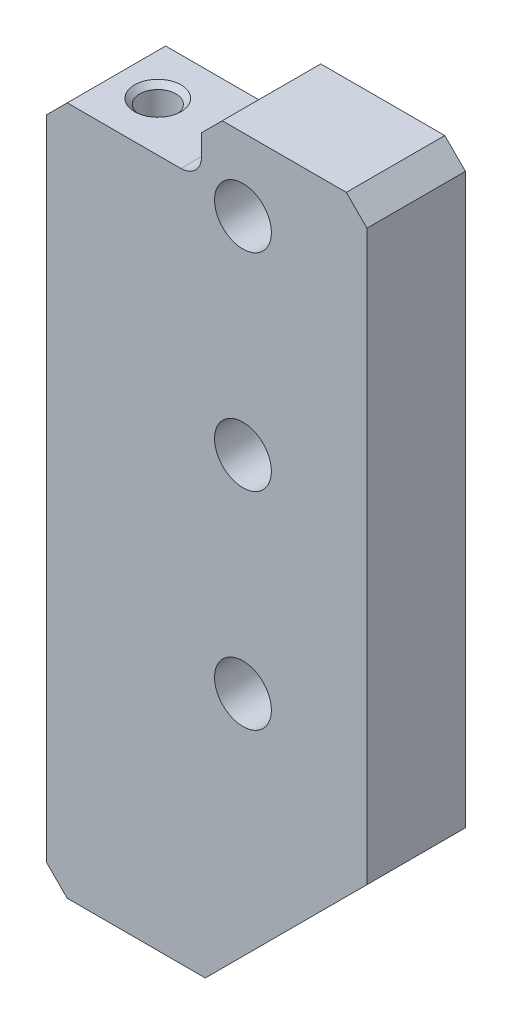
SolidWorks part; units mm, degrees
material "Plain Carbon Steel"
ref_plane "Front Plane" through (0, 0, 0) normal (0, 0, 1) x (1, 0, 0)
ref_plane "Top Plane" through (0, 0, 0) normal (0, 1, 0) x (1, 0, 0)
ref_plane "Right Plane" through (0, 0, 0) normal (1, 0, 0) x (0, 0, -1)
sketch "Sketch1" plane through (0, 0, 0) normal (0, 0, 1) x (1, 0, 0)
  line L0 (-160.8878, 18.5523) -> (-176.2477, 18.5523) construction
  line L1 (-176.2477, 85.1924) -> (-176.2477, 18.5523) construction
  line L2 (-176.2477, 85.1924) -> (-161.2477, 85.1924) construction
  line L3 (-161.2477, 85.1924) -> (-161.2477, 91.1924) construction
  line L4 (-161.2477, 91.1924) -> (-145.2477, 91.1924) construction
  line L5 (-145.2477, 91.1924) -> (-145.2477, 34.1924) construction
  line L6 (-145.2477, 34.1924) -> (-160.8878, 18.5523) construction
  line L7 (-168.7477, 96.1924) -> (-168.7477, 85.1924) construction
  line L8 (-170.2477, 96.1924) -> (-170.2477, 85.1924) construction
  line L9 (-171.7477, 96.1924) -> (-171.7477, 85.1924) construction
  line L10 (-160.8878, 18.5523) -> (-176.2477, 18.5523)
  line L11 (-176.2477, 85.1924) -> (-176.2477, 18.5523)
  line L12 (-176.2477, 85.1924) -> (-161.2477, 85.1924)
  line L13 (-161.2477, 85.1924) -> (-161.2477, 91.1924)
  line L14 (-161.2477, 91.1924) -> (-145.2477, 91.1924)
  line L15 (-145.2477, 91.1924) -> (-145.2477, 34.1924)
  line L16 (-145.2477, 34.1924) -> (-160.8878, 18.5523)
  line L17 (-168.7477, 96.1924) -> (-168.7477, 85.1924) construction
  line L18 (-170.2477, 96.1924) -> (-170.2477, 85.1924) construction
  line L19 (-171.7477, 96.1924) -> (-171.7477, 85.1924) construction
  line L20 (-168.7477, 85.1924) -> (-168.7477, 65.1924) construction
  line L21 (-168.7477, 65.1924) -> (-170.2477, 64.3264) construction
  line L22 (-170.2477, 64.3264) -> (-171.7477, 65.1924) construction
  line L23 (-171.7477, 65.1924) -> (-171.7477, 85.1924) construction
  line L24 (-168.7477, 65.1924) -> (-171.7477, 65.1924) construction
  circle A0 centre (-157.2477, 44.1924) radius 2.75 construction
  circle A1 centre (-157.2477, 64.1924) radius 2.75 construction
  circle A2 centre (-157.2477, 84.1924) radius 2.75 construction
  circle A3 centre (-169.2477, 84.1924) radius 2.75 construction
  circle A4 centre (-157.2477, 44.1924) radius 2.75
  circle A5 centre (-157.2477, 64.1924) radius 2.75
  circle A6 centre (-157.2477, 84.1924) radius 2.75
  circle A7 centre (-169.2477, 84.1924) radius 2.75 construction
  dimension "D1" = 120
  dimension "D2" = 20
extrude "Boss-Extrude1" add sketch "Sketch1" along normal blind 4.7625 and the other way blind 4.7625
sketch "Sketch2" plane through (0, 0, 0) normal (0, 0, 1) x (1, 0, 0)
  line L0 (-170.2477, 85.1924) -> (-171.9977, 85.1924)
  line L1 (-171.9977, 85.1924) -> (-171.9977, 80.1924)
  line L2 (-171.9977, 80.1924) -> (-171.4477, 79.8748)
  line L3 (-171.4477, 79.8748) -> (-171.4477, 65.0192)
  line L4 (-171.4477, 65.0192) -> (-170.2477, 64.3264)
  line L5 (-170.2477, 85.1924) -> (-170.2477, 64.3264)
  line L6 (-161.2477, 85.1924) -> (-176.2477, 85.1924) construction
  line L7 (-170.2477, 85.1924) -> (-170.2477, 95.5113) construction
  line L8 (-176.2477, 85.1924) -> (-161.2477, 85.1924) construction
  line L9 (-170.2477, 96.1924) -> (-170.2477, 85.1924) construction
  line L10 (-170.2477, 64.3264) -> (-171.7477, 65.1924) construction
  dimension "D1" = 3.5
  dimension "D2" = 5
  dimension "D3" = 2.4
revolve "Cut-Revolve1" cut sketch "Sketch2" angle 360 about L7
chamfer "Chamfer1" distance 2 angle 45 4 edges at (-176.2477, 18.5523, 0) (-145.2477, 91.1924, 0) (-161.2477, 91.1924, 0) (-176.2477, 85.1924, 0)
chamfer "Chamfer2" distance 0.5 angle 45 1 edges at (-168.4977, 85.1924, 0)
fillet "Fillet1" radius 2 1 edges at (-161.2477, 85.1924, 0)
